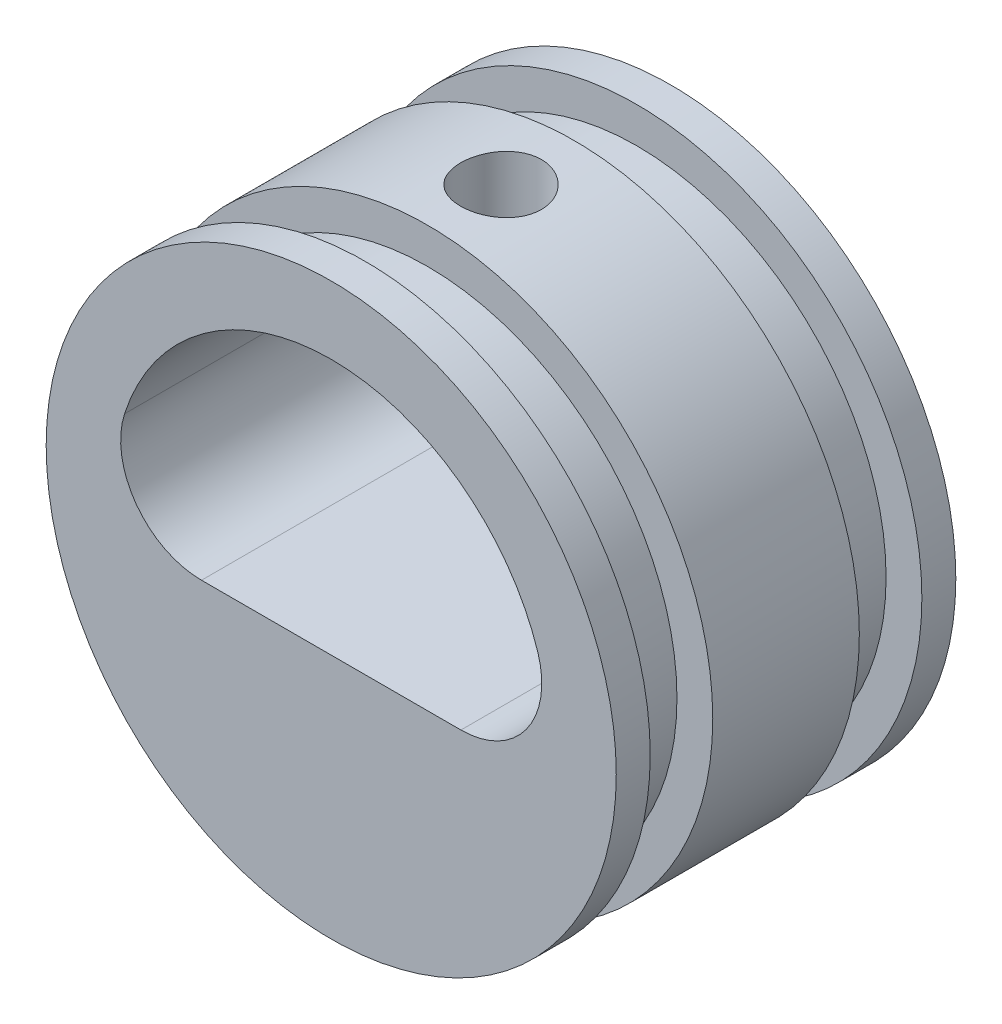
SolidWorks part; units mm, degrees
ref_plane "Front Plane" through (0, 0, 0) normal (0, 0, 1) x (1, 0, 0)
ref_plane "Top Plane" through (0, 0, 0) normal (0, 1, 0) x (1, 0, 0)
ref_plane "Right Plane" through (0, 0, 0) normal (1, 0, 0) x (0, 0, -1)
sketch "Sketch1" plane through (0, 0, 0) normal (0, 0, 1) x (1, 0, 0)
  circle A0 centre (0, 0) radius 16.7894
  dimension "D1" = 33.5788
extrude "Boss-Extrude1" add sketch "Sketch1" along normal blind 20
sketch "Sketch2" plane through (0, 0, 0) normal (1, 0, 0) x (0, 0, -1)
  line L0 (0, 16.7894) -> (-20, 16.7894) construction
  line L1 (-18, 16.7894) -> (-14.317, 16.7894)
  line L2 (-18, 16.7894) -> (-18, 14.6812)
  line L3 (-18, 14.6812) -> (-14.317, 14.6812)
  line L4 (-14.317, 16.7894) -> (-14.317, 14.6812)
  line L5 (-21.2407, 0) -> (1.9138, 0) construction
  line L6 (-20, 16.7894) -> (-20, -16.7894) construction
  line L7 (0, -16.7894) -> (0, 16.7894) construction
  line L8 (-2, 16.7894) -> (-5.683, 16.7894)
  line L9 (-2, 16.7894) -> (-2, 14.6812)
  line L10 (-2, 14.6812) -> (-5.683, 14.6812)
  line L11 (-5.683, 16.7894) -> (-5.683, 14.6812)
  dimension "D1" = 3.683
  dimension "D2" = 2.1082
  dimension "D3" = 2
  dimension "D4" = 2
revolve "Cut-Revolve1" cut sketch "Sketch2" angle 360 about L5
sketch "Sketch3" plane through (0, 0, 20) normal (0, 0, 1) x (1, 0, 0)
  line L0 (-12.5809, -2.3) -> (12.5809, -2.3)
  line L1 (-18.2206, 0) -> (27.3408, 0) construction
  arc A0 (12.5809, -2.3) -> (-12.5809, -2.3) centre (0, 0) ccw
  circle A1 centre (0, 0) radius 16.7894 construction
  dimension "D1" = 4
  dimension "D2" = 2.3
extrude "Cut-Extrude1" cut sketch "Sketch3" against normal through all
ref_point "Point1"
fillet "Fillet1" radius 4.7625 2 edges at (-12.5809, -2.3, 10) (12.5809, -2.3, 10)
ref_plane "Plane1" through (0, 16.7894, 0) normal (0, 1, 0) x (-1, 0, 0)
hole_wizard "3/16 (0.1875) Diameter Hole1" positions "Sketch6" profile "Sketch5" hole size "3/16" standard "Ansi Inch"
sketch "Sketch6" plane through (0, 16.7894, 0) normal (0, 1, 0) x (-1, 0, 0)
  line L3 (0, -3.916) -> (0, 34.5317) construction
  line L6 (16.7894, 20) -> (-16.7894, 20) construction
  line L7 (-16.7894, 0) -> (16.7894, 0) construction
  circle A0 centre (0, 10) radius 10 construction
  point P1 (0, 10)
sketch "Sketch5" plane through (0, 16.7894, 10) normal (1, 0, 0) x (0, 0, 1)
  line L0 (0, 0) -> (0, 12.9745)
  line L1 (0, 12.9745) -> (2.3812, 11.5437)
  line L2 (2.3812, 11.5437) -> (2.3813, 0)
  line L5 (2.3813, 0) -> (0, 0)
  line L10 (0, 12.9745) -> (-2.3813, 11.5437) construction
  line L11 (0, -6.35) -> (0, 107.95) construction
  dimension "Hole Dia." = 4.7625
  dimension "Hole Depth" = 11.5437
  dimension "Drill Angle" = 118
